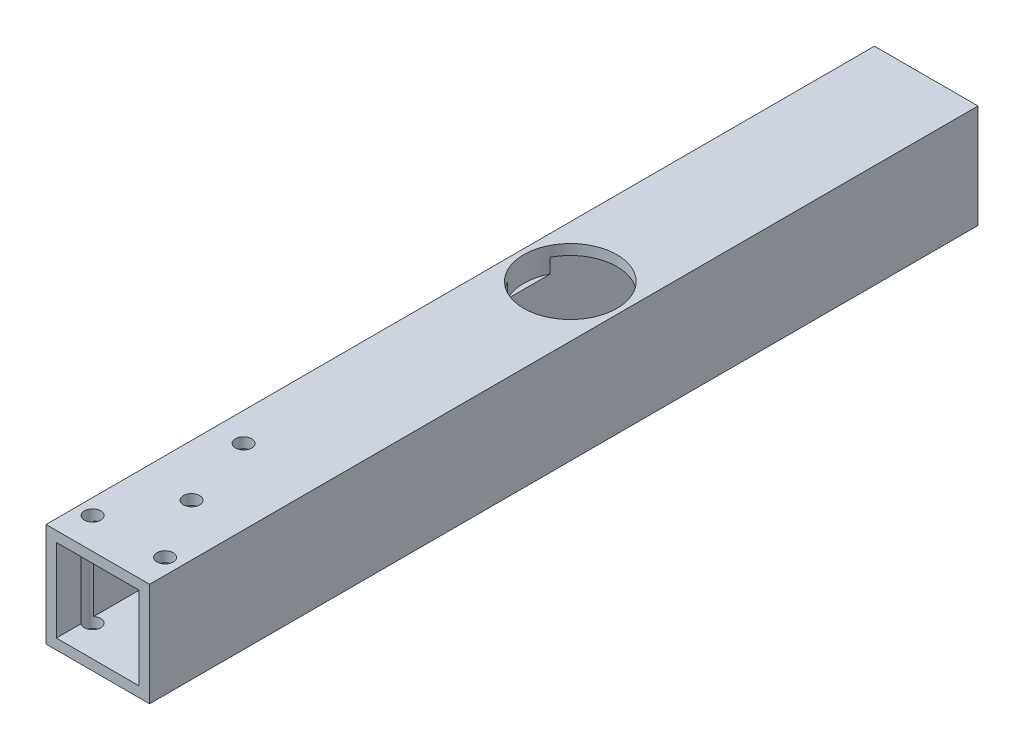
SolidWorks part; units mm, degrees
material "6061 Alloy"
ref_plane "Front Plane" through (0, 0, 0) normal (0, 0, 1) x (1, 0, 0)
ref_plane "Top Plane" through (0, 0, 0) normal (0, 1, 0) x (1, 0, 0)
ref_plane "Right Plane" through (0, 0, 0) normal (1, 0, 0) x (0, 0, -1)
sketch "Sketch1" plane through (0, 0, 0) normal (0, 0, 1) x (1, 0, 0)
  line L0 (-12.7, 12.7) -> (12.7, 12.7)
  line L2 (-15.875, 15.875) -> (15.875, 15.875)
  line L3 (-15.875, 15.875) -> (-15.875, -15.875)
  line L4 (-15.875, -15.875) -> (15.875, -15.875)
  line L5 (15.875, 15.875) -> (15.875, -15.875)
  line L10 (12.7, 12.7) -> (12.7, -12.7)
  line L11 (-12.7, -12.7) -> (12.7, -12.7)
  line L12 (-12.7, 12.7) -> (-12.7, -12.7)
  point P12 (0, 15.875)
  point P14 (15.875, 0)
  dimension "Wall Thickness" = 3.175
  dimension "Outside Width" = 31.75
  dimension "Outside Height" = 31.75
  dimension "Inside Height" = 25.4
  dimension "Inside Width" = 25.4
sketch "Sketch2" plane through (0, 0, 0) normal (1, 0, 0) x (0, 0, -1)
  line L0 (127, 0) -> (-127, 0)
  point P4 (0, 0)
  point P7 (-127, 0)
  point P10 (127, 0)
  dimension "Length" = 254
sketch "Sketch3" plane through (0, 0, 0) normal (0, 0, 1) x (1, 0, 0)
  line L21 (15.875, 15.875) -> (-15.875, 15.875)
  line L22 (15.875, -15.875) -> (15.875, 15.875)
  line L23 (-15.875, -15.875) -> (15.875, -15.875)
  line L24 (-15.875, 15.875) -> (-15.875, -15.875)
  line L25 (15.875, 15.875) -> (-15.875, 15.875)
  line L26 (15.875, -15.875) -> (15.875, 15.875)
  line L27 (-15.875, -15.875) -> (15.875, -15.875)
  line L28 (-15.875, 15.875) -> (-15.875, -15.875)
  line L29 (12.7, 12.7) -> (-12.7, 12.7)
  line L30 (12.7, -12.7) -> (12.7, 12.7)
  line L31 (-12.7, -12.7) -> (12.7, -12.7)
  line L32 (-12.7, 12.7) -> (-12.7, -12.7)
  line L33 (12.7, 12.7) -> (-12.7, 12.7)
  line L34 (12.7, -12.7) -> (12.7, 12.7)
  line L35 (-12.7, -12.7) -> (12.7, -12.7)
  line L36 (-12.7, 12.7) -> (-12.7, -12.7)
  dimension "D1" = 0
  dimension "D2" = 0
extrude "Boss-Extrude1" add sketch "Sketch3" along normal up to vertex (127 mm away) and the other way up to vertex (127 mm away) up to point (0, 0, 127) other way up to point (0, 0, -127)
sketch "Drawing Reference" plane through (0, 0, 0) normal (1, 0, 0) x (0, 0, -1)
  line L0 (-127, 0) -> (127, 0) construction
  line L1 (0, -15.875) -> (0, 15.875) construction
  line L2 (-127, -15.875) -> (127, -15.875) construction
  line L5 (-127, 15.875) -> (127, 15.875) construction
  point P7 (-104.14, 0)
  point P8 (104.14, 0)
  dimension "D1" = 22.86
sketch "Sketch4" plane through (0, 15.875, 0) normal (0, 1, 0) x (1, 0, 0)
  line L0 (0, -127) -> (0, -117.475) construction
  line L1 (15.875, -127) -> (-15.875, -127) construction
  line L2 (0, -117.475) -> (11.1125, -117.475) construction
  line L3 (0, -117.475) -> (-11.1125, -117.475) construction
  line L4 (0, -117.475) -> (0, 17.8816) construction
  line L5 (0, -117.475) -> (0, -98.2472) construction
  point P5 (-7.1119, -75.1713)
  dimension "D1" = 135.3566
  dimension "D2" = 22.225
  dimension "D3" = 9.525
hole_wizard "#10 Clearance Hole1" positions "Sketch5" profile "Sketch6" hole size "#10" standard "ANSI Inch" end condition through all
sketch "Sketch5" plane through (0, 15.875, 0) normal (0, 1, 0) x (1, 0, 0)
  point P0 (-11.1125, -117.475)
  point P3 (11.1125, -117.475)
  point P7 (0, -98.2472)
  point P10 (-7.1119, -75.1713)
sketch "Sketch6" plane through (-11.1125, 15.875, 117.475) normal (1, 0, 0) x (0, 0, 1)
  line L0 (0, 0) -> (0, 31.75)
  line L1 (0, 31.75) -> (2.4892, 31.75)
  line L2 (2.4892, 31.75) -> (2.4892, 0)
  line L5 (2.4892, 0) -> (0, 0)
  line L11 (0, -6.35) -> (0, 107.95) construction
  dimension "Thru Hole Dia." = 4.9784
  dimension "Thru Hole Depth" = 31.75
sketch "Sketch7" plane through (0, 15.875, 0) normal (0, 1, 0) x (1, 0, 0)
  circle A0 centre (0, 17.8816) radius 14.2875
  dimension "D1" = 28.575
extrude "Cut-Extrude1" cut sketch "Sketch7" against normal blind 7.62
sketch "Sketch8" plane through (0, -15.875, 0) normal (0, -1, 0) x (1, 0, 0)
  circle A0 centre (0, -17.8816) radius 14.2875
  dimension "D1" = 28.575
extrude "Cut-Extrude2" cut sketch "Sketch8" against normal blind 7.62
equation "\"D1@Drawing Reference\"=\"Outside Width@Sketch1\" * 0.72"
